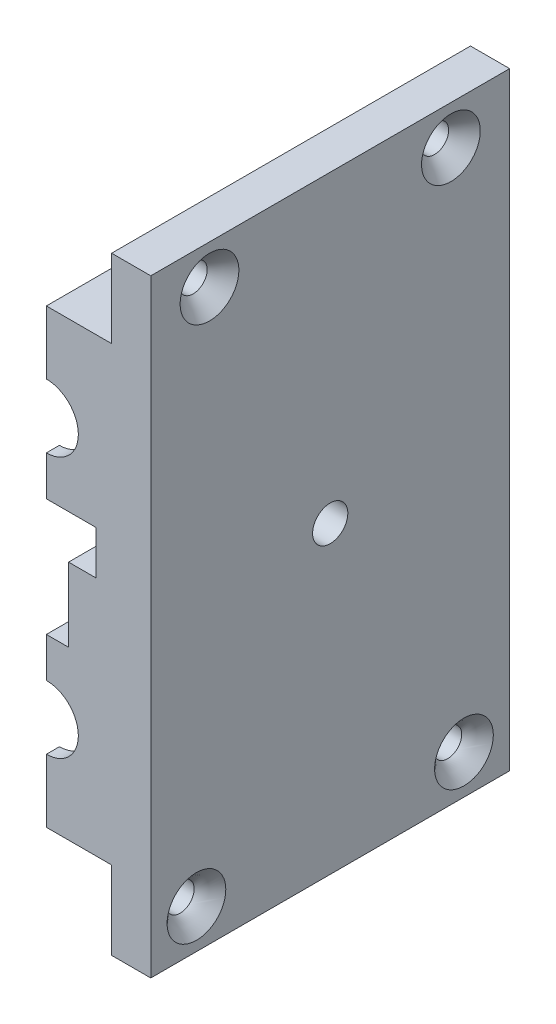
SolidWorks part; units mm, degrees
ref_plane "Front Plane" through (0, 0, 0) normal (0, 0, 1) x (1, 0, 0)
ref_plane "Top Plane" through (0, 0, 0) normal (0, 1, 0) x (1, 0, 0)
ref_plane "Right Plane" through (0, 0, 0) normal (1, 0, 0) x (0, 0, -1)
sketch "Sketch1" plane through (0, 0, 0) normal (0, 0, 1) x (1, 0, 0)
  line L0 (0, 0) -> (0, -93.2)
  line L1 (0, -93.2) -> (-6, -93.2)
  line L2 (-6, -93.2) -> (-6, -81.2)
  line L3 (-6, -81.2) -> (-16, -81.2)
  line L4 (-16, -81.2) -> (-16, -74.2)
  line L5 (-16, -59) -> (-16, -44.3)
  line L6 (-16, -44.3) -> (-8.4, -44.3)
  line L7 (-8.4, -44.3) -> (-8.4, -37.6)
  line L8 (-8.4, -37.6) -> (-16, -37.6)
  line L9 (-16, -37.6) -> (-16, -34.2)
  line L10 (-16, -19) -> (-16, -12)
  line L11 (-16, -12) -> (-6, -12)
  line L12 (-6, -12) -> (-6, 0)
  line L13 (-6, 0) -> (0, 0)
  arc A0 (-16, -74.2) -> (-16, -59) centre (-16, -66.6) ccw
  arc A1 (-16, -34.2) -> (-16, -19) centre (-16, -26.6) ccw
  dimension "D6" = 7.6
  dimension "D7" = 7.6
  dimension "D1" = 6
  dimension "D2" = 12
  dimension "D3" = 12
  dimension "D4" = 14.7
  dimension "D5" = 40
  dimension "D8" = 7
  dimension "D9" = 3.4
  dimension "D11" = 10
  dimension "D12" = 10
extrude "Boss-Extrude1" add sketch "Sketch1" along normal blind 55
ref_plane "Plane1" through (0, 0, 28.5) normal (0, 0, -1) x (-1, 0, 0)
sketch "Sketch2" plane through (0, 0, 28.5) normal (0, 0, -1) x (-1, 0, 0)
  line L0 (16, -34.2) -> (16, -31.5)
  line L1 (16, -21.7) -> (16, -19)
  arc A0 (16, -19) -> (16, -34.2) centre (16, -26.6) ccw
  arc A1 (16, -21.7) -> (16, -31.5) centre (16, -26.6) ccw
  dimension "D1" = 4.9
extrude "Boss-Extrude2" add sketch "Sketch2" along normal blind 2
sketch "Sketch3" plane through (0, 0, 28.5) normal (0, 0, -1) x (-1, 0, 0)
  line L0 (16, -74.2) -> (16, -71.5)
  line L1 (16, -61.7) -> (16, -59)
  arc A0 (16, -59) -> (16, -74.2) centre (16, -66.6) ccw
  arc A1 (16, -61.7) -> (16, -71.5) centre (16, -66.6) ccw
  dimension "D1" = 4.9
extrude "Boss-Extrude3" add sketch "Sketch3" along normal blind 2
ref_plane "Plane2" through (0, 0, 2) normal (0, 0, -1) x (-1, 0, 0)
sketch "Sketch4" plane through (0, 0, 2) normal (0, 0, -1) x (-1, 0, 0)
  line L1 (16, -59) -> (16, -61.7)
  line L2 (16, -74.2) -> (16, -81.2) construction
  line L4 (16, -71.5) -> (16, -74.2)
  line L5 (16, -19) -> (16, -21.7)
  line L6 (16, -31.5) -> (16, -34.2)
  arc A1 (16, -59) -> (16, -74.2) centre (16, -66.6) ccw construction
  arc A2 (16, -74.2) -> (16, -59) centre (16, -66.6) cw
  arc A4 (16, -61.7) -> (16, -71.5) centre (16, -66.6) ccw
  arc A5 (16, -34.2) -> (16, -19) centre (16, -26.6) cw
  arc A6 (16, -21.7) -> (16, -31.5) centre (16, -26.6) ccw
  dimension "D1" = 4.9
  dimension "D2" = 4.9
extrude "Boss-Extrude5" add sketch "Sketch4" along normal blind 2
ref_plane "Plane3" through (0, 0, 53) normal (0, 0, -1) x (-1, 0, 0)
sketch "Sketch5" plane through (0, 0, 53) normal (0, 0, -1) x (-1, 0, 0)
  line L0 (16, -19) -> (16, -21.7)
  line L1 (16, -31.5) -> (16, -34.2)
  line L2 (16, -59) -> (16, -61.7)
  line L3 (16, -71.5) -> (16, -74.2)
  arc A0 (16, -19) -> (16, -34.2) centre (16, -26.6) ccw construction
  arc A1 (16, -34.2) -> (16, -19) centre (16, -26.6) cw
  arc A2 (16, -21.7) -> (16, -31.5) centre (16, -26.6) ccw
  arc A3 (16, -74.2) -> (16, -59) centre (16, -66.6) cw
  arc A4 (16, -61.7) -> (16, -71.5) centre (16, -66.6) ccw
  dimension "D1" = 4.9
extrude "Boss-Extrude6" add sketch "Sketch5" against normal blind 2
sketch "Sketch7" plane through (0, 0, 55) normal (0, 0, 1) x (1, 0, 0)
  line L1 (-16, -44.3) -> (-12.6, -44.3)
  line L2 (-16, -44.3) -> (-16, -55.6)
  line L3 (-16, -55.6) -> (-12.6, -55.6)
  line L4 (-12.6, -44.3) -> (-12.6, -55.6)
  dimension "D1" = 3.4
  dimension "D2" = 11.3
extrude "Cut-Extrude2" cut sketch "Sketch7" against normal up to surface (55 mm away) up to face at (-9.9375, -45.1875, 0)
sketch "Sketch8" plane through (0, 0, 0) normal (1, 0, 0) x (0, 0, -1)
  line L0 (-55, -93.2) -> (-55, 0) construction
  line L1 (0, -93.2) -> (0, 0) construction
  line L2 (-55, 0) -> (0, 0) construction
  line L3 (-55, -93.2) -> (0, -93.2) construction
  circle A0 centre (-46, -6) radius 2.15
  circle A1 centre (-9, -6) radius 2.15
  circle A2 centre (-7, -87.2) radius 2.15
  circle A3 centre (-48, -87.2) radius 2.15
  dimension "D1" = 4.3
  dimension "D2" = 4.3
  dimension "D3" = 4.3
  dimension "D4" = 4.3
  dimension "D5" = 9
  dimension "D6" = 9
  dimension "D7" = 7
  dimension "D8" = 7
  dimension "D9" = 6
  dimension "D10" = 6
  dimension "D11" = 6
  dimension "D12" = 6
extrude "Cut-Extrude3" cut sketch "Sketch8" against normal up to surface (6 mm away) up to face at (-6, -6, 27.5)
sketch "Sketch9" plane through (0, 0, 0) normal (1, 0, 0) x (0, 0, -1)
  line L0 (-55, 0) -> (0, 0) construction
  line L1 (-55, -93.2) -> (-55, 0) construction
  circle A0 centre (-27.5, -46.6) radius 2.7
  dimension "D1" = 5.4
  dimension "D2" = 46.6
  dimension "D3" = 27.5
extrude "Cut-Extrude4" cut sketch "Sketch9" against normal up to surface (12.6 mm away) up to face at (-12.6, -49.95, 27.5)
ref_plane "Plane4" through (-2.5, 0, 0) normal (1, 0, 0) x (0, 0, -1)
sketch "Sketch12" plane through (-2.5, 0, 0) normal (1, 0, 0) x (0, 0, -1)
  circle A0 centre (-46, -6) radius 2.15 construction
  circle A1 centre (-46, -6) radius 2.15
sketch "Sketch13" plane through (0, 0, 0) normal (1, 0, 0) x (0, 0, -1)
  circle A0 centre (-46, -6) radius 4.5
  dimension "D1" = 9
loft "Cut-Loft1" cut profiles "Sketch13", "Sketch12" connector at (0, -9.0908, 49.2707) connector at (-2.5, -7.7977, 47.1793)
pattern_linear "LPattern1" count 2 spacing 37 along (0, 0, -1) of "Cut-Loft1"
sketch "Sketch14" plane through (-2.5, 0, 0) normal (1, 0, 0) x (0, 0, -1)
  circle A0 centre (-48, -87.2) radius 2.15 construction
  circle A1 centre (-48, -87.2) radius 2.15
sketch "Sketch15" plane through (0, 0, 0) normal (1, 0, 0) x (0, 0, -1)
  circle A0 centre (-48, -87.2) radius 4.5
  dimension "D1" = 9
loft "Cut-Loft2" cut profiles "Sketch14", "Sketch15" connector at (-2.5, -88.8038, 46.5681) connector at (0, -88.245, 43.623)
pattern_linear "LPattern2" count 2 spacing 41 along (0, 0, -1) of "Cut-Loft2"
